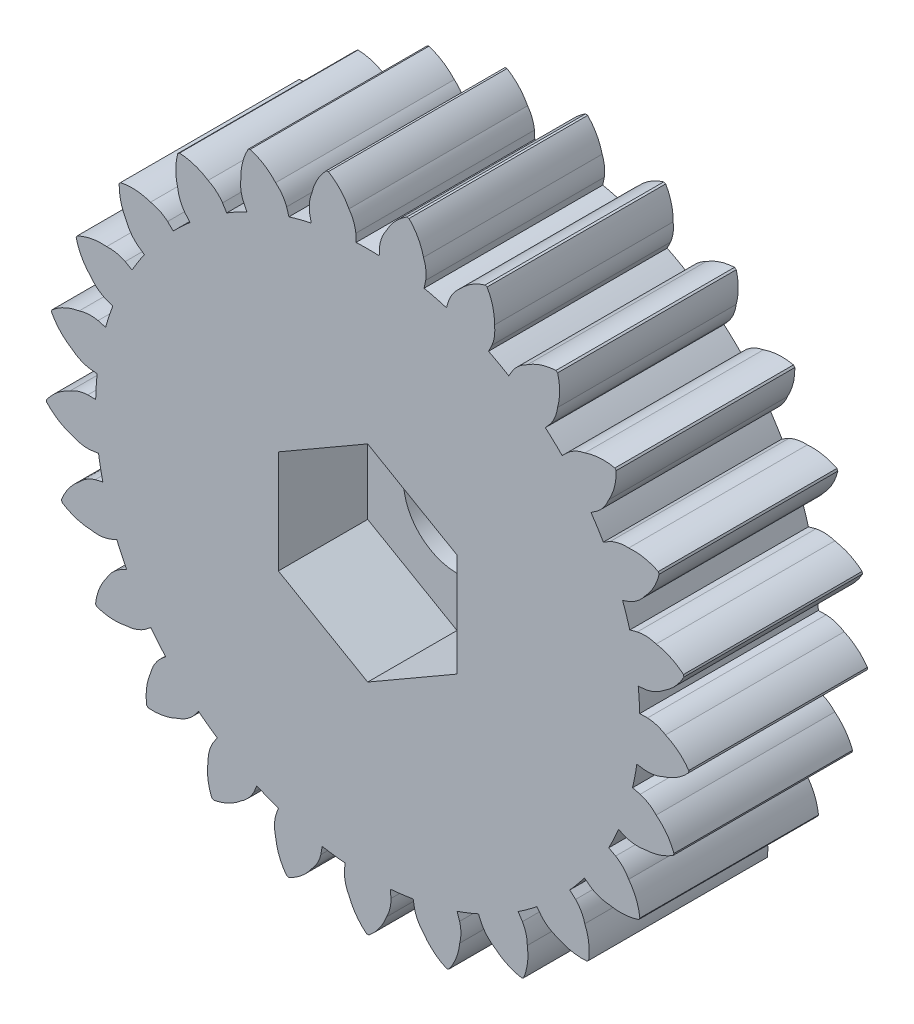
SolidWorks part; units mm, degrees
ref_plane "Plano frontal" through (0, 0, 0) normal (0, 0, 1) x (1, 0, 0)
ref_plane "Plano superior" through (0, 0, 0) normal (0, 1, 0) x (1, 0, 0)
ref_plane "Plano direito" through (0, 0, 0) normal (1, 0, 0) x (0, 0, -1)
sketch "Esboço1" plane through (0, 0, -10) normal (0, 0, 1) x (1, 0, 0)
  circle A0 centre (175.26, 0) radius 7.14
  circle A1 centre (175.26, 0) radius 18.009
  circle A3 centre (175.26, 0) radius 7.14 construction
  circle A6 centre (175.26, 0) radius 7.14 construction
  dimension "D1" = 36.018
extrude "Ressalto-extrusão1" add sketch "Esboço1" against normal up to surface (5 mm away) contours A0
extrude "Ressalto-extrusão2" add sketch "Esboço1<3>" along normal up to surface (10 mm away) contours A1
sketch "Esboço1<3>" plane through (0, 0, -10) normal (0, 0, 1) x (1, 0, 0) same geometry as "Esboço1"
sketch "Esboço2" plane through (0, 0, 0) normal (0, 0, 1) x (1, 0, 0)
  circle A0 centre (175.26, 0) radius 3
  dimension "D1" = 6
extrude "Corte-extrusão1" cut sketch "Esboço2" against normal through all
sketch "Esboço3" plane through (0, 0, 0) normal (0, 0, 1) x (1, 0, 0)
  line L0 (175.26, 0) -> (175.26, 18.009) construction
  line L1 (174.6141, 15.2168) -> (174.5954, 15.6554)
  line L2 (175.9059, 15.2168) -> (175.9246, 15.6554)
  circle A0 centre (175.26, 0) radius 15.2305 construction
  circle A1 centre (175.26, 0) radius 15.6695 construction
  circle A2 centre (175.26, 0) radius 16.675 construction
  circle A3 centre (175.26, 0) radius 18.009 construction
  arc A4 (174.5954, 15.6554) -> (174.213, 16.6421) centre (172.5655, 15.4361) ccw
  arc A5 (174.213, 16.6421) -> (173.0614, 17.8743) centre (171.4284, 15.1938) ccw
  arc A6 (175.9246, 15.6554) -> (176.307, 16.6421) centre (177.9545, 15.4361) cw
  arc A7 (176.307, 16.6421) -> (177.4586, 17.8743) centre (179.0916, 15.1938) cw
  arc A8 (174.6141, 15.2168) -> (175.9059, 15.2168) centre (175.26, 0) cw
  arc A9 (177.4586, 17.8743) -> (173.0614, 17.8743) centre (175.26, -0.0012) ccw
  point P29 (174.6047, 15.4361)
  dimension "D1" = 30.461
  dimension "D2" = 33.35
  dimension "D3" = 31.339
  dimension "D4" = 2.094
extrude "Corte-extrusão2" cut sketch "Esboço3" against normal blind 10 body kept at (176.307, 16.6421, 0)
pattern_circular "PadrãoCircular1" count 25 over 360 about axis through (175.26, 0, 0) along (0, 0, -1) of "Corte-extrusão2"
sketch "Esboço4" plane through (0, 0, 0) normal (0, 0, 1) x (1, 0, 0)
  line L1 (175.26, 5.7735) -> (170.26, 2.8868)
  line L2 (170.26, 2.8868) -> (170.26, -2.8868)
  line L3 (170.26, -2.8868) -> (175.26, -5.7735)
  line L4 (175.26, -5.7735) -> (180.26, -2.8868)
  line L5 (180.26, -2.8868) -> (180.26, 2.8868)
  line L6 (180.26, 2.8868) -> (175.26, 5.7735)
  circle A0 centre (175.26, 0) radius 5 construction
  dimension "D1" = 10
extrude "Corte-extrusão3" cut sketch "Esboço4" against normal blind 5
